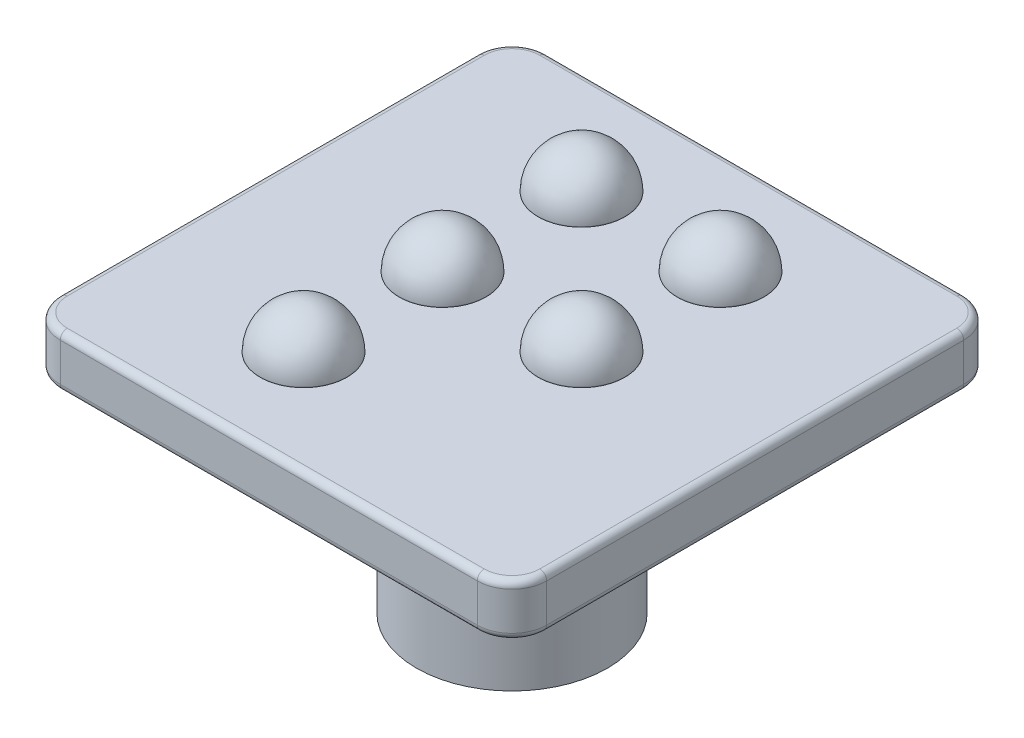
SolidWorks part; units mm, degrees
ref_plane "Front Plane" through (0, 0, 0) normal (0, 0, 1) x (1, 0, 0)
ref_plane "Top Plane" through (0, 0, 0) normal (0, 1, 0) x (1, 0, 0)
ref_plane "Right Plane" through (0, 0, 0) normal (1, 0, 0) x (0, 0, -1)
sketch "Sketch1" plane through (0, 0, 0) normal (0, 1, 0) x (1, 0, 0)
  line L1 (-7.3247, 4.3967) -> (4.6753, 4.3967)
  line L2 (-8.3247, 3.3967) -> (-8.3247, -8.6033)
  line L3 (-7.3247, -9.6033) -> (4.6753, -9.6033)
  line L4 (5.6753, 3.3967) -> (5.6753, -8.6033)
  arc A0 (-8.3247, -8.6033) -> (-7.3247, -9.6033) centre (-7.3247, -8.6033) ccw
  arc A1 (4.6753, -9.6033) -> (5.6753, -8.6033) centre (4.6753, -8.6033) ccw
  arc A2 (4.6753, 4.3967) -> (5.6753, 3.3967) centre (4.6753, 3.3967) cw
  arc A3 (-7.3247, 4.3967) -> (-8.3247, 3.3967) centre (-7.3247, 3.3967) ccw
  point P8 (5.6753, -9.6033)
  point P11 (5.6753, 4.3967)
  point P14 (-8.3247, 4.3967)
  dimension "D3" = 1
  dimension "D1" = 14
  dimension "D2" = 14
extrude "Boss-Extrude1" add sketch "Sketch1" along normal blind 1.5
sketch "Sketch2" plane through (0, 0, 0) normal (0, -1, 0) x (1, 0, 0)
  line L0 (-7.3247, 9.6033) -> (4.6753, 9.6033) construction
  line L1 (5.6753, 8.6033) -> (5.6753, -3.3967) construction
  line L2 (-1.3247, -4.3967) -> (-1.3247, 9.6033) construction
  line L3 (-8.3247, 2.6033) -> (5.6753, 2.6033) construction
  line L4 (-8.3247, -3.3967) -> (-8.3247, 8.6033) construction
  circle A0 centre (-1.3247, 2.6033) radius 2.75
  dimension "D1" = 7
  dimension "D2" = 7
extrude "Boss-Extrude2" add sketch "Sketch2" along normal blind 6
sketch "Sketch3" plane through (0, -6, 0) normal (0, -1, 0) x (1, 0, 0)
  line L0 (-1.3247, 5.3533) -> (-1.3247, -0.1467) construction
  line L1 (-3.3247, 3.1533) -> (0.6753, 3.1533)
  line L2 (-3.3247, 3.1533) -> (-3.3247, 2.0533)
  line L3 (-3.3247, 2.0533) -> (0.6753, 2.0533)
  line L4 (0.6753, 3.1533) -> (0.6753, 2.0533)
  line L5 (-1.8747, 4.6033) -> (-0.7747, 4.6033)
  line L6 (-1.8747, 4.6033) -> (-1.8747, 0.6033)
  line L7 (-1.8747, 0.6033) -> (-0.7747, 0.6033)
  line L8 (-0.7747, 4.6033) -> (-0.7747, 0.6033)
  line L9 (-4.0747, 2.6033) -> (1.4253, 2.6033) construction
  circle A3 centre (-1.3247, 2.6033) radius 2.75 construction
  circle A4 centre (-1.3247, 2.6033) radius 2.75 construction
  dimension "D7" = 0.55
  dimension "D1" = 4
  dimension "D2" = 1.1
  dimension "D3" = 1.1
  dimension "D4" = 4
  dimension "D8" = 0.55
extrude "Cut-Extrude1" cut sketch "Sketch3" against normal blind 6 contours L8 L5 L6 L1 | L1 L8 L3 L4 | L8 L1 L6 L3 | L6 L1 L2 L3 | L8 L3 L6 L7 region at (-2.5997, -6, 2.6033) region at (-1.3247, -6, 3.8783) region at (-1.3247, -6, 2.6033) region at (-0.0497, -6, 2.6033) region at (-1.3247, -6, 1.3283)
chamfer "Chamfer1" distance 0.3 angle 45 12 edges at (-1.3247, -6, 0.6033) (-1.8747, -6, 1.3283) (-2.5997, -6, 2.0533) (-3.3247, -6, 2.6033) (-2.5997, -6, 3.1533) (-0.7747, -6, 1.3283) (-0.0497, -6, 2.0533) (0.6753, -6, 2.6033) (-0.0497, -6, 3.1533) (-0.7747, -6, 3.8783) (-1.3247, -6, 4.6033) (-1.8747, -6, 3.8783)
fillet "Fillet1" radius 1 1 edges at (-1.3247, 0, -0.1467)
sketch "Sketch4" plane through (0, 1.5, 0) normal (0, 1, 0) x (1, 0, 0)
  line L0 (-1.3247, 4.3967) -> (-1.3247, -9.6033) construction
  line L1 (4.6753, 4.3967) -> (-7.3247, 4.3967) construction
  line L2 (-7.3247, -9.6033) -> (4.6753, -9.6033) construction
  line L3 (5.6753, -2.6033) -> (-8.3247, -2.6033) construction
  line L4 (-8.3247, 3.3967) -> (-8.3247, -8.6033) construction
  line L5 (5.6753, -8.6033) -> (5.6753, 3.3967) construction
  line L6 (-3.3247, 4.3967) -> (-3.3247, -9.6033) construction
  line L7 (0.6753, 4.3967) -> (0.6753, -9.6033) construction
  line L8 (-8.3247, 1.3967) -> (5.6753, 1.3967) construction
  line L9 (5.6753, -6.6033) -> (-8.3247, -6.6033) construction
  circle A0 centre (-3.3247, 1.3967) radius 1.25
  circle A1 centre (0.6753, -2.6033) radius 1.25
  circle A2 centre (-3.3247, -2.6033) radius 1.25
  circle A3 centre (-3.3247, -6.6033) radius 1.25
  circle A5 centre (0.6753, 1.3967) radius 1.25
  dimension "D1" = 4
  dimension "D2" = 4
  dimension "D3" = 2
  dimension "D4" = 2
extrude "Boss-Extrude3" add sketch "Sketch4" along normal blind 0.01
dome "Dome1" faces to dome 1 distance 1.25 reverse direction no elliptical dome no face at (-3.3247, 1.51, -0.1467) parameters "D1"=1.25
dome "Dome2" faces to dome 1 distance 1.25 reverse direction no elliptical dome no face at (0.6753, 1.51, -0.1467) parameters "D1"=1.25
dome "Dome3" faces to dome 1 distance 1.25 reverse direction no elliptical dome no face at (-3.3247, 1.51, 3.8533) parameters "D1"=1.25
dome "Dome4" faces to dome 1 distance 1.25 reverse direction no elliptical dome no face at (0.6753, 1.51, 3.8533) parameters "D1"=1.25
dome "Dome5" faces to dome 1 distance 1.25 reverse direction no elliptical dome no face at (-3.3247, 1.51, 7.8533) parameters "D1"=1.25
fillet "Fillet3" radius 0.2 16 edges at (5.3824, 1.5, -4.1038) (5.6753, 1.5, 2.6033) (5.3824, 1.5, 9.3104) (-1.3247, 1.5, 9.6033) (-8.0318, 1.5, 9.3104) (-8.0318, 1.5, -4.1038) (-8.3247, 1.5, 2.6033) (-1.3247, 1.5, -4.3967) (5.3824, 0, 9.3104) (5.6753, 0, 2.6033) (5.3824, 0, -4.1038) (-1.3247, 0, -4.3967) (-8.0318, 0, -4.1038) (-8.3247, 0, 2.6033) (-8.0318, 0, 9.3104) (-1.3247, 0, 9.6033)
